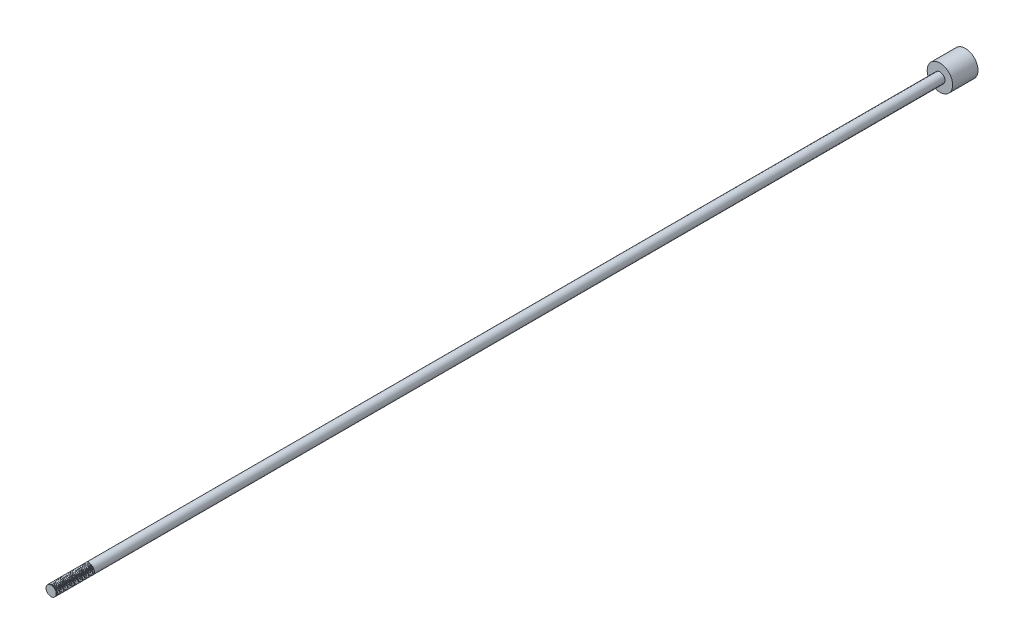
SolidWorks part; units mm, degrees
ref_plane "前视基准面" through (0, 0, 0) normal (0, 0, 1) x (1, 0, 0)
ref_plane "上视基准面" through (0, 0, 0) normal (0, 1, 0) x (1, 0, 0)
ref_plane "右视基准面" through (0, 0, 0) normal (1, 0, 0) x (0, 0, -1)
sketch "草图1" plane through (0, 0, 0) normal (0, 0, 1) x (1, 0, 0)
  circle A0 centre (0, 0) radius 5
extrude "凸台-拉伸1" add sketch "草图1" along normal blind 10
sketch "草图2" plane through (0, 0, 10) normal (0, 0, 1) x (1, 0, 0)
  circle A0 centre (0, 0) radius 2
extrude "凸台-拉伸2" add sketch "草图2" along normal blind 350
thread "螺纹线1" pitch 0.3175 method cut profile "螺纹线轮廓1" start angle 0, offset 0, length 15, pitch 0.3175, diameter 4
ref_plane "基准面1" through (-2, 0, 360) normal (0, -1, 0) x (-1, 0, 0)
sketch "螺纹线轮廓1" plane through (-2, 0, 360) normal (0, -1, 0) x (-1, 0, 0)
  line L0 (0, 0) -> (0, 0.3175) construction
  line L11 (0, 0) -> (0, 0.2778)
  line L12 (0, 0.2778) -> (-0.1719, 0.1786)
  line L13 (-0.1719, 0.1786) -> (-0.1719, 0.0992)
  line L15 (-0.1719, 0.0992) -> (0, 0)
  line L17 (-0.1719, 0.1389) -> (0, 0.1389) construction
  point P2 (0, 0)
  dimension "Pitch" = 0.3175
  dimension "Profile_Angle" = 60
  dimension "Profile_Land" = 0.0794
  dimension "Profile_Height" = 0.1719
